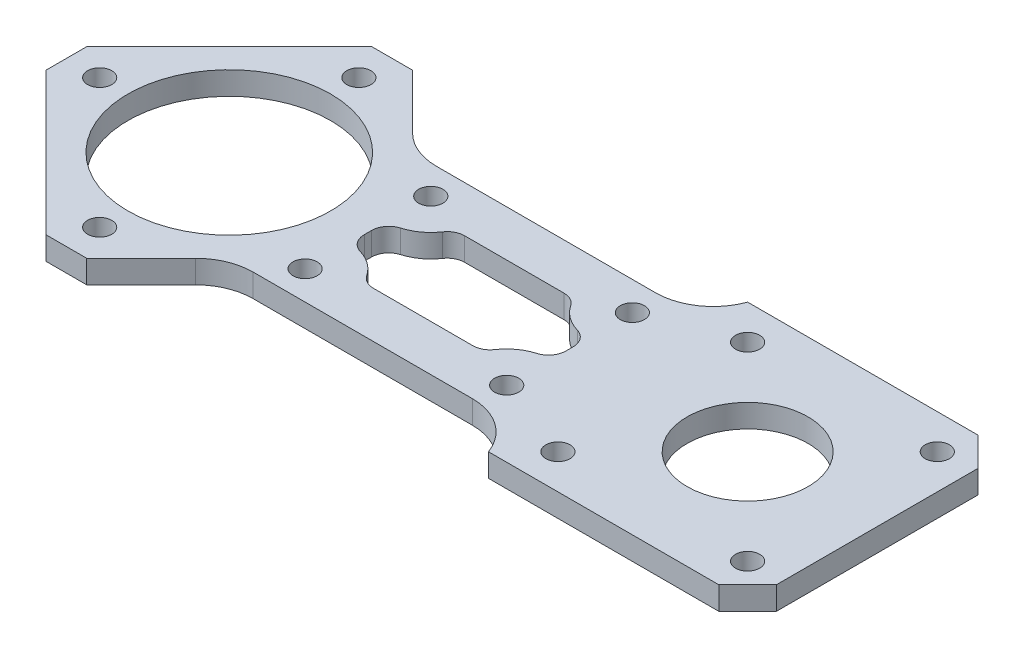
SolidWorks part; units mm, degrees
ref_plane "前视基准面" through (0, 0, 0) normal (0, 0, 1) x (1, 0, 0)
ref_plane "上视基准面" through (0, 0, 0) normal (0, 1, 0) x (1, 0, 0)
ref_plane "右视基准面" through (0, 0, 0) normal (1, 0, 0) x (0, 0, -1)
sketch "草图1" plane through (0, 0, 0) normal (0, 1, 0) x (1, 0, 0)
  line L0 (0, 0) -> (-31.8198, 0) construction
  line L1 (0, 31.8198) -> (-31.8198, 0)
  line L2 (-31.8198, 0) -> (0, -31.8198)
  line L3 (0, -31.8198) -> (15.9099, -15.9099)
  line L4 (15.9099, 15.9099) -> (0, 31.8198)
  line L5 (0, 0) -> (90, 0) construction
  line L6 (0, 0) -> (45, 77.9423) construction
  line L7 (45, 77.9423) -> (90, 0) construction
  line L8 (15.9099, 15.9099) -> (67.5, 15.9099)
  line L9 (15.9099, -15.9099) -> (67.5, -15.9099)
  line L10 (90, 0) -> (67.5, -22.5) construction
  line L11 (67.5, 22.5) -> (67.5, 15.9099)
  line L12 (67.5, -22.5) -> (112.5, -22.5)
  line L13 (112.5, -22.5) -> (112.5, 22.5)
  line L14 (112.5, 22.5) -> (67.5, 22.5)
  line L15 (67.5, -15.9099) -> (67.5, -22.5)
  line L16 (0, 0) -> (15.9099, 15.9099) construction
  line L17 (0, 0) -> (15.9099, -15.9099) construction
  circle A0 centre (0, 14) radius 2.1
  circle A1 centre (14, 0) radius 2.1
  circle A2 centre (0, -14) radius 2.1
  circle A3 centre (-14, 0) radius 2.1
  circle A4 centre (0, 0) radius 22.5 construction
  arc A5 (45, -77.9423) -> (45, 77.9423) centre (0, 0) ccw construction
  arc A6 (45, 77.9423) -> (45, -77.9423) centre (90, 0) ccw construction
  circle A7 centre (90, 0) radius 10.5
  circle A8 centre (90, 0) radius 22.5 construction
  circle A9 centre (0, 22.5) radius 2.1
  circle A11 centre (0, -22.5) radius 2.1
  circle A12 centre (0, 0) radius 10
  circle A13 centre (0, 0) radius 14 construction
  circle A14 centre (-22.5, 0) radius 2.1
  dimension "D1" = 4.2
  dimension "D2" = 20
  dimension "D3" = 4.2
  dimension "D4" = 4.2
  dimension "D5" = 4.2
  dimension "D6" = 45
  dimension "D9" = 180
  dimension "D10" = 180
  dimension "D11" = 21
  dimension "D14" = 4.2
  dimension "D15" = 4.2
  dimension "D17" = 4.2
  dimension "D7" = 180
  dimension "D8" = 90
  dimension "D12" = 135
  dimension "D13" = 45
extrude "凸台-拉伸1" add sketch "草图1" along normal blind 4
chamfer "倒角1" distance 5 angle 45 5 edges at (112.5, 2, 22.5) (112.5, 2, -22.5) (0, 2, 31.8198) (-31.8198, 2, 0) (0, 2, -31.8198)
fillet "圆角1" radius 10 4 edges at (15.9099, 2, -15.9099) (15.9099, 2, 15.9099) (67.5, 2, 15.9099) (67.5, 2, -15.9099)
sketch "草图2" plane through (0, 0, 0) normal (0, -1, 0) x (1, 0, 0)
  line L0 (39.0757, 15.9099) -> (39.0757, 10.9099) construction
  line L1 (20.052, 15.9099) -> (58.0993, 15.9099) construction
  line L2 (39.0757, 10.9099) -> (24.0757, 10.9099) construction
  line L3 (39.0757, 10.9099) -> (59.0757, 10.9099) construction
  line L4 (110, 20) -> (90, 0) construction
  line L5 (112.5, 17.5) -> (107.5, 22.5) construction
  line L6 (110, -20) -> (90, 0) construction
  line L7 (107.5, -22.5) -> (112.5, -17.5) construction
  line L8 (90, 22.5) -> (90, -22.5) construction
  line L9 (67.5, 22.5) -> (107.5, 22.5) construction
  line L10 (107.5, -22.5) -> (67.5, -22.5) construction
  line L11 (70, -20) -> (90, 0) construction
  line L12 (70, 20) -> (90, 0) construction
  line L13 (0, 0) -> (90, 0) construction
  line L14 (39.0757, -10.9099) -> (59.0757, -10.9099) construction
  line L15 (39.0757, -10.9099) -> (24.0757, -10.9099) construction
  line L16 (39.0757, -15.9099) -> (39.0757, -10.9099) construction
  circle A0 centre (106.4645, 16.4645) radius 2.1
  circle A1 centre (106.4645, -16.4645) radius 2.1
  circle A2 centre (73.5355, -16.4645) radius 2.1
  circle A3 centre (73.5355, 16.4645) radius 2.1
  circle A4 centre (24.0757, 10.9099) radius 2.1
  circle A5 centre (59.0757, 10.9099) radius 2.1
  circle A6 centre (59.0757, -10.9099) radius 2.1
  circle A7 centre (24.0757, -10.9099) radius 2.1
  dimension "D3" = 4.2
  dimension "D4" = 4.2
  dimension "D5" = 20
  dimension "D6" = 15
  dimension "D8" = 4.2
  dimension "D9" = 4.2
  dimension "D1" = 5
  dimension "D2" = 5
  dimension "D7" = 5
extrude "切除-拉伸1" cut sketch "草图2" against normal blind 10
sketch "草图3" plane through (0, 4, 0) normal (0, 1, 0) x (1, 0, 0)
  line L0 (0, 0) -> (90, 0) construction
  line L1 (74.689, 83.8667) -> (39.0757, 15.9099)
  line L2 (58.0993, 15.9099) -> (20.052, 15.9099) construction
  line L3 (78, 70.7956) -> (49.2367, 15.9099)
  line L6 (39.0757, 15.9099) -> (49.2367, 15.9099)
  line L7 (82.6607, 79.6891) -> (47.0474, 11.7323) construction
  line L8 (78, 77.9423) -> (78, 49.0248) construction
  line L9 (98.5819, 22.5) -> (107.5, 22.5)
  line L10 (107.5, 22.5) -> (67.5, 22.5) construction
  line L12 (74.689, 83.8667) -> (81.3477, 83.8667)
  line L13 (45, 77.9423) -> (78, 77.9423) construction
  line L14 (81.3477, 83.8667) -> (107.5, 22.5)
  line L16 (78, 70.7956) -> (98.5819, 22.5)
  circle A9 centre (78, 77.9423) radius 1.6
  point P5 (45, 77.9423)
  point P9 (67.5, 22.5)
  point P11 (40.0576, 81.3442)
  point P14 (50.7578, 79.6297)
  dimension "D1" = 9
  dimension "D2" = 360
  dimension "D4" = 33
extrude "凸台-拉伸2" add sketch "草图3" against normal blind 3
sketch "草图4" plane through (0, 4, 0) normal (0, 1, 0) x (1, 0, 0)
  circle A0 centre (0, 0) radius 17.6
  dimension "D1" = 35.2
extrude "切除-拉伸2" cut sketch "草图4" against normal blind 10
sketch "草图5" plane through (0, 4, 0) normal (0, 1, 0) x (1, 0, 0)
  line L2 (39.0757, 15.9099) -> (20.052, 15.9099) construction
  line L3 (20.052, -15.9099) -> (58.0993, -15.9099) construction
  line L4 (24.0757, 3.2021) -> (24.0757, -3.2021)
  line L5 (59.0757, 3.2021) -> (59.0757, -3.2021)
  line L15 (31.1757, -7.9099) -> (51.9757, -7.9099)
  line L17 (51.9757, 7.9099) -> (31.1757, 7.9099)
  arc A0 (24.0757, 3.2021) -> (31.1757, 7.9099) centre (24.0757, 10.9099) ccw
  arc A1 (51.9757, 7.9099) -> (59.0757, 3.2021) centre (59.0757, 10.9099) ccw
  arc A2 (59.0757, -3.2021) -> (51.9757, -7.9099) centre (59.0757, -10.9099) ccw
  arc A3 (31.1757, -7.9099) -> (24.0757, -3.2021) centre (24.0757, -10.9099) ccw
  dimension "D1" = 8
  dimension "D2" = 8
extrude "切除-拉伸3" cut sketch "草图5" against normal blind 31.8
fillet "圆角6" radius 3 8 edges at (59.0757, 2, 3.2021) (59.0757, 2, -3.2021) (51.9757, 2, -7.9099) (51.9757, 2, 7.9099) (31.1757, 2, 7.9099) (24.0757, 2, 3.2021) (24.0757, 2, -3.2021) (31.1757, 2, -7.9099)
fillet "圆角7" radius 4 1 edges at (49.2367, 2.5, -15.9099)
sketch "草图6" plane through (0, 4, 0) normal (0, 1, 0) x (1, 0, 0)
  line L0 (67.5, 22.5) -> (52.6903, 22.5)
  line L1 (52.3059, 21.7666) -> (78, 70.7956) construction
  line L2 (52.3059, 21.7666) -> (52.6903, 22.5)
  line L3 (58.0993, 15.9099) -> (55.8489, 15.9099) construction
  line L4 (58.0993, 15.9099) -> (55.8489, 15.9099)
  arc A0 (52.3059, 21.7666) -> (55.8489, 15.9099) centre (55.8489, 19.9099) ccw construction
  arc A1 (52.3059, 21.7666) -> (55.8489, 15.9099) centre (55.8489, 19.9099) ccw
  arc A2 (58.0993, 15.9099) -> (67.5, 22.5) centre (58.0993, 25.9099) ccw construction
  arc A3 (58.0993, 15.9099) -> (67.5, 22.5) centre (58.0993, 25.9099) ccw
extrude "凸台-拉伸3" add sketch "草图6" against normal blind 3
fillet "圆角8" radius 4 3 edges at (78, 2.5, -70.7956) (98.5819, 2.5, -22.5) (52.6903, 2.5, -22.5)
chamfer "倒角4" distance 15 angle 38 1 edges at (39.0757, 2.5, -15.9099) first distance on face at (39.0757, 1.6667, -15.9099)
sketch "草图7" plane through (0, 4, 0) normal (0, 1, 0) x (1, 0, 0)
  line L0 (32.197, 15.9099) -> (56.1516, 15.9099)
  line L2 (52.5536, 31.8142) -> (27.154, 11.9698)
  line L3 (51.5056, 30.9954) -> (32.197, 15.9099)
  line L4 (56.1516, 15.9099) -> (59.3025, 17.5)
  arc A3 (51.5056, 30.9954) -> (59.3025, 17.5) centre (59.3025, 26.5) ccw
  dimension "D1" = 5
extrude "切除-拉伸4" cut sketch "草图7" against normal blind 3
fillet "圆角11" radius 5 2 edges at (24.0757, 2.5, -15.9099) (49.4753, 2.5, -35.7542)
sketch "草图8" plane through (0, 4, 0) normal (0, 1, 0) x (1, 0, 0)
  line L0 (81.3477, 83.8667) -> (83.3477, 83.8667)
  line L1 (83.3477, 83.8667) -> (85.2534, 74.7019)
  line L2 (107.5, 22.5) -> (81.3477, 83.8667) construction
  line L3 (74.689, 83.8667) -> (72.689, 83.8667)
  line L4 (72.689, 83.8667) -> (69.8862, 74.7019)
  line L5 (74.689, 83.8667) -> (49.9759, 36.7094) construction
  line L6 (69.8862, 74.7019) -> (74.689, 83.8667)
  line L7 (81.3477, 83.8667) -> (85.2534, 74.7019)
extrude "凸台-拉伸4" add sketch "草图8" against normal blind 3
fillet "圆角12" radius 5 2 edges at (69.8862, 2.5, -74.7019) (85.2534, 2.5, -74.7019)
chamfer "倒角5" distance 1.5 angle 38 2 edges at (72.689, 2.5, -83.8667) (83.3477, 2.5, -83.8667) first distance on face at (71.3558, 2.5, -79.5072) first distance on face at (78.0184, 2.5, -83.8667)
sketch "草图9" plane through (0, 4, 0) normal (0, 1, 0) x (1, 0, 0)
  line L0 (22.354, 15.9099) -> (58.0993, 15.9099)
  line L1 (128.2054, 15.9099) -> (92.9499, 93.1491)
  line L2 (92.9499, 93.1491) -> (54.9681, 93.1491)
  line L3 (54.9681, 93.1491) -> (22.354, 15.9099)
  line L4 (67.5, 22.5) -> (112.7131, 22.5)
  line L5 (112.7131, 22.5) -> (128.2054, 15.9099)
  line L9 (-28.2843, 0) -> (68.0993, 0) construction
  line L10 (-28.2843, 3.5355) -> (-28.2843, -3.5355) construction
  arc A0 (67.5, -22.5) -> (58.0993, -15.9099) centre (58.0993, -25.9099) ccw construction
  arc A2 (67.5, 22.5) -> (58.0993, 15.9099) centre (58.0993, 25.9099) cw
extrude "切除-拉伸5" cut sketch "草图9" against normal blind 10
